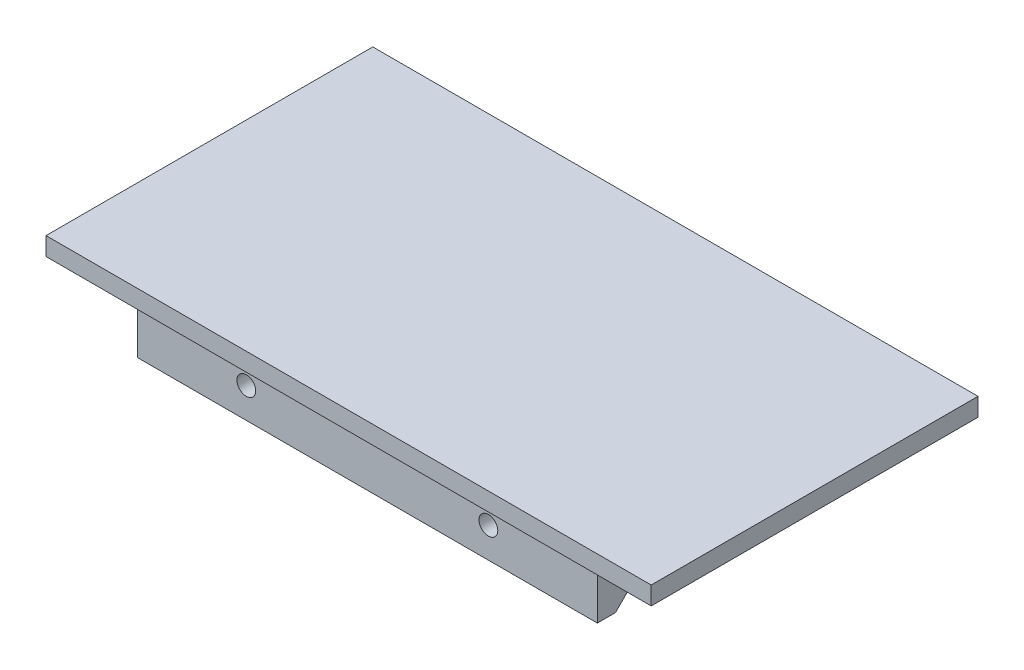
SolidWorks part; units mm, degrees
ref_plane "Front Plane" through (0, 0, 0) normal (0, 0, 1) x (1, 0, 0)
ref_plane "Top Plane" through (0, 0, 0) normal (0, 1, 0) x (1, 0, 0)
ref_plane "Right Plane" through (0, 0, 0) normal (1, 0, 0) x (0, 0, -1)
sketch "Sketch1" plane through (0, 0, 0) normal (0, 1, 0) x (1, 0, 0)
  line L1 (-47, -24) -> (47, -24) construction
  line L2 (-47, -24) -> (-47, 24) construction
  line L3 (-47, 24) -> (47, 24) construction
  line L4 (47, -24) -> (47, 24) construction
  line L5 (-47, -24) -> (47, 24) construction
  line L6 (-47, 24) -> (47, -24) construction
  line L7 (50, -27) -> (-50, -27)
  line L8 (50, -27) -> (50, 27)
  line L9 (50, 27) -> (-50, 27)
  line L10 (-50, -27) -> (-50, 27)
  line L11 (50, -27) -> (-50, 27) construction
  line L12 (50, 27) -> (-50, -27) construction
  point P0 (0, 0)
  point P5 (0, 0)
  dimension "D1" = 94
  dimension "D2" = 48
  dimension "D3" = 3
  dimension "D4" = 3
extrude "Boss-Extrude1" add sketch "Sketch1" along normal blind 3
sketch "Sketch2" plane through (0, 0, 0) normal (0, -1, 0) x (1, 0, 0)
  line L0 (-38, 23.9) -> (-38, 20.9)
  line L1 (-38, 20.9) -> (38, 20.9)
  line L2 (38, 20.9) -> (38, 23.9)
  line L3 (38, 23.9) -> (-38, 23.9)
  line L4 (-50, 27) -> (50, 27) construction
  line L5 (0, 20.9) -> (0, 0) construction
  line L6 (-50, -27) -> (-50, 27) construction
  line L7 (-38, -23.9) -> (38, -23.9)
  line L8 (38, -23.9) -> (38, -20.9)
  line L9 (38, -20.9) -> (-38, -20.9)
  line L10 (-38, -20.9) -> (-38, -23.9)
  line L11 (50, -27) -> (-50, -27) construction
  point P13 (0, 0)
  point P18 (0, 0)
  point P19 (0, 0)
  dimension "D1" = 3.1
  dimension "D2" = 3
  dimension "D3" = 12
  dimension "D4" = 3.1
extrude "Boss-Extrude2" add sketch "Sketch2" along normal blind 10
chamfer "Chamfer1" distance 10 angle 45 2 edges at (0, 0, -20.9) (0, 0, 20.9)
sketch "Sketch3" plane through (0, -10, 0) normal (0, -1, 0) x (1, 0, 0)
  line L0 (0, 0) -> (0, 20.9) construction
  line L1 (-38, 20.9) -> (38, 20.9) construction
  line L2 (-20, 20.9) -> (20, 20.9) construction
  line L3 (-25, 20.9) -> (-25, 10.9)
  line L4 (38, 10.9) -> (-38, 10.9) construction
  line L5 (-25, 10.9) -> (-15, 10.9)
  line L6 (-15, 10.9) -> (-15, 20.9)
  line L7 (-15, 20.9) -> (-25, 20.9)
  line L8 (-20, 20.9) -> (-20, 10.9) construction
  line L9 (15, 10.9) -> (15, 20.9)
  line L10 (25, 10.9) -> (15, 10.9)
  line L11 (25, 20.9) -> (25, 10.9)
  line L12 (15, 20.9) -> (25, 20.9)
  point P7 (0, 20.9)
  dimension "D1" = 40
  dimension "D2" = 10
extrude "Cut-Extrude1" cut sketch "Sketch3" against normal up to surface (10 mm away) up to face at (0, 0, 17.4)
sketch "Sketch4" plane through (0, 0, 23.9) normal (0, 0, 1) x (1, 0, 0)
  line L0 (0, 0) -> (0, -10) construction
  line L1 (38, -10) -> (-38, -10) construction
  line L2 (-20, -5) -> (20, -5) construction
  circle A0 centre (-20, -5) radius 1.55
  circle A1 centre (20, -5) radius 1.55
  point P7 (0, -5)
  point P8 (0, -5)
  dimension "D2" = 3.1
  dimension "D3" = 3.1
  dimension "D1" = 40
extrude "Cut-Extrude2" cut sketch "Sketch4" against normal up to surface (3 mm away) up to face at (-20, -5, 20.9)
